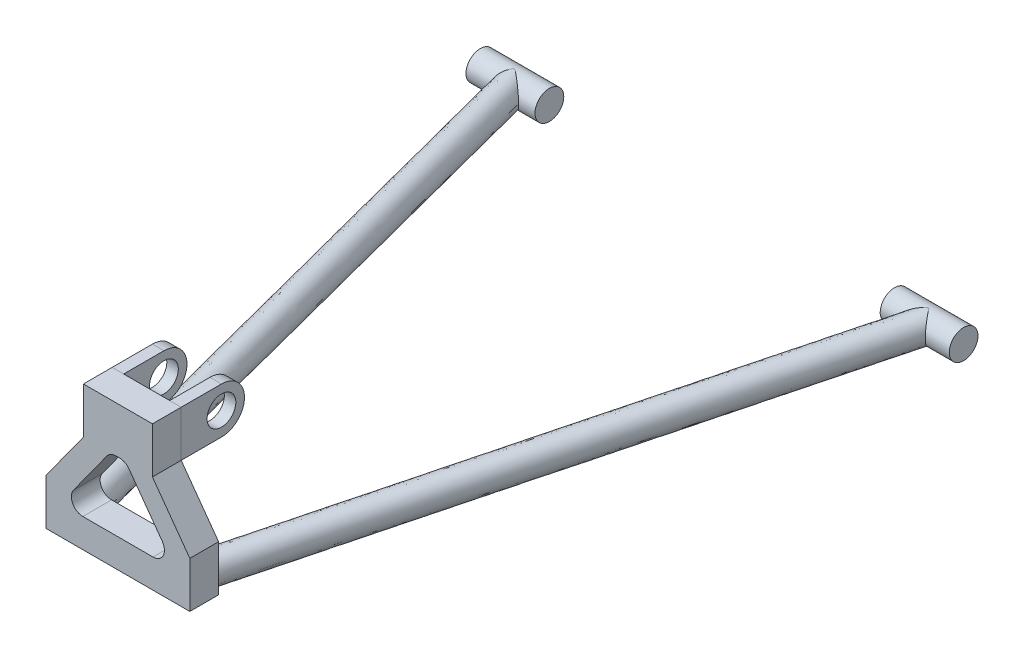
SolidWorks part; units mm, degrees
ref_plane "Front Plane" through (0, 0, 0) normal (0, 0, 1) x (1, 0, 0)
ref_plane "Top Plane" through (0, 0, 0) normal (0, 1, 0) x (1, 0, 0)
ref_plane "Right Plane" through (0, 0, 0) normal (1, 0, 0) x (0, 0, -1)
sketch "Sketch1" plane through (0, 0, 0) normal (0, 1, 0) x (1, 0, 0)
  line L0 (-36, 0) -> (36, 0) construction
  line L1 (-36, 0) -> (-10, -100)
  line L2 (-10, -100) -> (10, -100)
  line L5 (-42, 0) -> (-30, 0)
  line L6 (30, 0) -> (42, 0)
  line L7 (10, -100) -> (36, 0)
  line L8 (0, -100) -> (0, 0) construction
  dimension "D1" = 72
  dimension "D2" = 100
  dimension "D3" = 12
  dimension "D4" = 20
sketch "Sketch16" plane through (0, 0, 0) normal (0, 0, 1) x (1, 0, 0)
  line L0 (-42, 0) -> (-30, 0) construction
  circle A0 centre (-36, 0) radius 2.5
  circle A1 centre (36, 0) radius 2.5
  dimension "D1" = 5
extrude "Boss-Extrude1" add sketch "Sketch16" along direction (0.2516, 0, -0.9678) on the side of the normal up to vertex (100 mm away) contours A1 up to point (10, 0, 100)
extrude "Boss-Extrude2" add sketch "Sketch16<3>" along direction (0.2516, 0, 0.9678) on the side of the normal up to vertex (100 mm away) separate body contours A0 region at (-36, 0, 0) up to point (-10, 0, 100)
sketch "Sketch16<3>" plane through (0, 0, 0) normal (0, 0, 1) x (1, 0, 0) same geometry as "Sketch16"
sketch "Sketch17" plane through (0, 0, 0) normal (1, 0, 0) x (0, 0, -1)
  line L0 (0, -2.5) -> (0, 2.5) construction
  circle A0 centre (0, 0) radius 2.5
  dimension "D1" = 5
extrude "Cut-Extrude2" cut sketch "Sketch17" against normal through all and the other way through all
extrude "Boss-Extrude4" add sketch "Sketch17<3>" along normal blind 12 from vertex separate body starting at point (30, 0, 0)
sketch "Sketch17<3>" plane through (0, 0, 0) normal (1, 0, 0) x (0, 0, -1) same geometry as "Sketch17"
extrude "Boss-Extrude5" add sketch "Sketch17<4>" along normal blind 12 from vertex separate body starting at point (-42, 0, 0)
sketch "Sketch17<4>" plane through (0, 0, 0) normal (1, 0, 0) x (0, 0, -1) same geometry as "Sketch17"
sketch "Sketch22" plane through (0, 0, 0) normal (0, 0, 1) x (1, 0, 0)
  line L0 (-12.5, -2.5) -> (12.5, -2.5)
  line L1 (-6, 22.5) -> (-6, 14.5)
  line L2 (6, 22.5) -> (-6, 22.5)
  line L3 (-6, 14.5) -> (-12.5, 5.5)
  line L4 (0, 22.5) -> (0, -2.5) construction
  line L5 (-12.5, 5.5) -> (-12.5, -2.5)
  line L6 (12.5, 5.5) -> (12.5, -2.5)
  line L7 (6, 22.5) -> (6, 14.5)
  line L8 (6, 14.5) -> (12.5, 5.5)
  line L9 (-6.0982, 2.5) -> (6.0982, 2.5)
  line L10 (7.7155, 5.6631) -> (1.9306, 13.673)
  line L11 (0.3132, 14.5) -> (-0.3132, 14.5)
  line L12 (-1.9306, 13.673) -> (-7.7155, 5.6631)
  circle A0 centre (-10, 0) radius 2.5 construction
  circle A1 centre (10, 0) radius 2.5 construction
  arc A2 (1.9306, 13.673) -> (0.3132, 14.5) centre (0.3132, 12.505) ccw
  arc A3 (-0.3132, 14.5) -> (-1.9306, 13.673) centre (-0.3132, 12.505) ccw
  arc A4 (7.7155, 5.6631) -> (6.0982, 2.5) centre (6.0982, 4.495) cw
  arc A5 (-6.0982, 2.5) -> (-7.7155, 5.6631) centre (-6.0982, 4.495) cw
  point P25 (10, 2.5)
  point P28 (-10, 2.5)
  dimension "D7" = 1.995
  dimension "D1" = 12
  dimension "D2" = 25
  dimension "D3" = 8
  dimension "D4" = 25
  dimension "D5" = 8
  dimension "D6" = 5
extrude "Boss-Extrude7" add sketch "Sketch22" along normal blind 5 from vertex separate body starting at point (10, 0, 100)
sketch "Sketch23" plane through (0, 0, 100) normal (0, 0, -1) x (-1, 0, 0)
  line L0 (-6, 22.5) -> (-4, 22.5)
  line L1 (-6, 22.5) -> (6, 22.5) construction
  line L2 (-4, 22.5) -> (-4, 14.5)
  line L3 (-4, 14.5) -> (-6, 14.5)
  line L4 (-6, 14.5) -> (-6, 22.5)
  line L5 (0, 22.5) -> (0, 14.5) construction
  line L6 (-0.3132, 14.5) -> (0.3132, 14.5) construction
  line L7 (6, 22.5) -> (4, 22.5)
  line L8 (6, 14.5) -> (6, 22.5)
  line L9 (4, 14.5) -> (6, 14.5)
  line L10 (4, 22.5) -> (4, 14.5)
  dimension "D1" = 2
extrude "Boss-Extrude8" add sketch "Sketch23" along normal blind 11 separate body
sketch "Sketch24" plane through (-6, 0, 0) normal (-1, 0, 0) x (0, 0, 1)
  line L0 (100, 14.5) -> (100, 22.5) construction
  line L1 (93, 18.5) -> (100, 18.5) construction
  line L2 (100, 22.5) -> (100, 14.5) construction
  line L3 (89, 22.5) -> (100, 22.5) construction
  line L4 (89, 14.5) -> (100, 14.5) construction
  line L5 (93, 22.5) -> (86, 22.5)
  line L6 (86, 22.5) -> (86, 14.5)
  line L8 (86, 14.5) -> (93, 14.5)
  circle A0 centre (93, 18.5) radius 2.5
  arc A1 (93, 22.5) -> (93, 14.5) centre (93, 18.5) ccw
  dimension "D1" = 7
  dimension "D2" = 5
extrude "Cut-Extrude5" cut sketch "Sketch24" along normal through all and the other way through all
